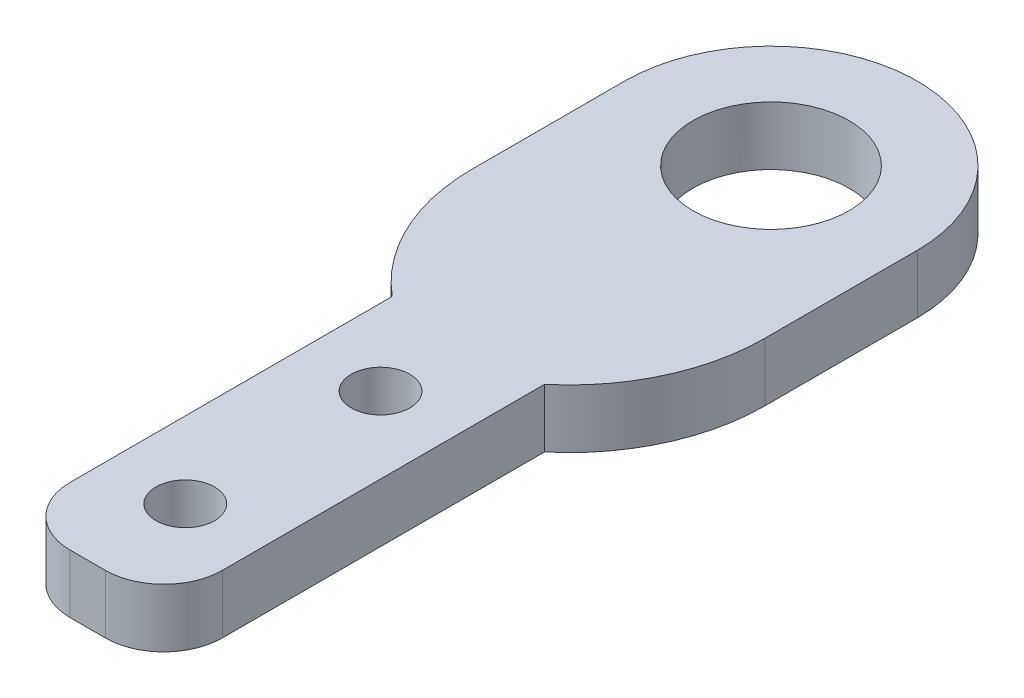
SolidWorks part; units mm, degrees
ref_plane "前视基准面" through (0, 0, 0) normal (0, 0, 1) x (1, 0, 0)
ref_plane "上视基准面" through (0, 0, 0) normal (0, 1, 0) x (1, 0, 0)
ref_plane "右视基准面" through (0, 0, 0) normal (1, 0, 0) x (0, 0, -1)
sketch "草图1" plane through (0, 0, 0) normal (0, 1, 0) x (1, 0, 0)
  line L1 (-7.5, -29) -> (7.5, -29)
  line L2 (-7.5, -29) -> (-7.5, 29)
  line L4 (7.5, -29) -> (7.5, 29)
  line L5 (-7.5, -29) -> (7.5, 29) construction
  line L6 (-7.5, 29) -> (7.5, -29) construction
  arc A0 (-7.5, 29) -> (7.5, 29) centre (0, 29) cw
  point P0 (0, 0)
  dimension "D1" = 15
  dimension "D2" = 58
extrude "凸台-拉伸1" add sketch "草图1" along normal blind 3
sketch "草图2" plane through (0, 3, 0) normal (0, 1, 0) x (1, 0, 0)
  circle A0 centre (0, 29) radius 4
  dimension "D1" = 8
extrude "切除-拉伸1" cut sketch "草图2" against normal blind 8
sketch "草图3" plane through (0, 0, 0) normal (0, -1, 0) x (1, 0, 0)
  circle A0 centre (0, 1) radius 1.5
  circle A1 centre (0, -9) radius 1.5
  arc A2 (-7.5, -29) -> (7.5, -29) centre (0, -29) ccw construction
  dimension "D1" = 3
  dimension "D3" = 20
  dimension "D2" = 10
extrude "切除-拉伸2" cut sketch "草图3" against normal blind 3
sketch "草图4" plane through (0, 0, 0) normal (0, -1, 0) x (1, 0, 0)
  line L0 (-7.5, -13.5) -> (-3.9, -13.5)
  line L1 (-7.5, -29) -> (-7.5, 29) construction
  line L2 (-3.9, -13.5) -> (-3.9, 26.5)
  line L4 (-3.9, 26.5) -> (3.9, 26.5)
  line L5 (3.9, 26.5) -> (3.9, -13.5)
  line L6 (3.9, -13.5) -> (7.5, -13.5)
  line L7 (7.5, 29) -> (7.5, -29) construction
  line L9 (-7.5, 29) -> (7.5, 29) construction
  line L10 (-7.5, -13.5) -> (-7.5, 29)
  line L11 (-7.5, 29) -> (7.5, 29)
  line L12 (7.5, 29) -> (7.5, -13.5)
  dimension "D1" = 7.8
  dimension "D2" = 3.6
  dimension "D3" = 40
  dimension "D4" = 2.5
extrude "切除-拉伸3" cut sketch "草图4" against normal blind 10
fillet "圆角1" radius 10 2 edges at (7.5, 1.5, -13.5) (-7.5, 1.5, -13.5)
sketch "草图5" plane through (0, 3, 0) normal (0, 1, 0) x (1, 0, 0)
  line L0 (-3.9, 13.5) -> (-3.9, -26.5) construction
  line L1 (-3.9, -6) -> (3.9, -6)
  line L2 (-3.9, -6) -> (-3.9, -26.5)
  line L3 (-3.9, -26.5) -> (3.9, -26.5)
  line L4 (3.9, -6) -> (3.9, -26.5)
  circle A0 centre (0, -1) radius 1.5 construction
  dimension "D1" = 5
extrude "切除-拉伸4" cut sketch "草图5" against normal blind 10
fillet "圆角3" radius 3 2 edges at (3.9, 1.5, 6) (-3.9, 1.5, 6)
